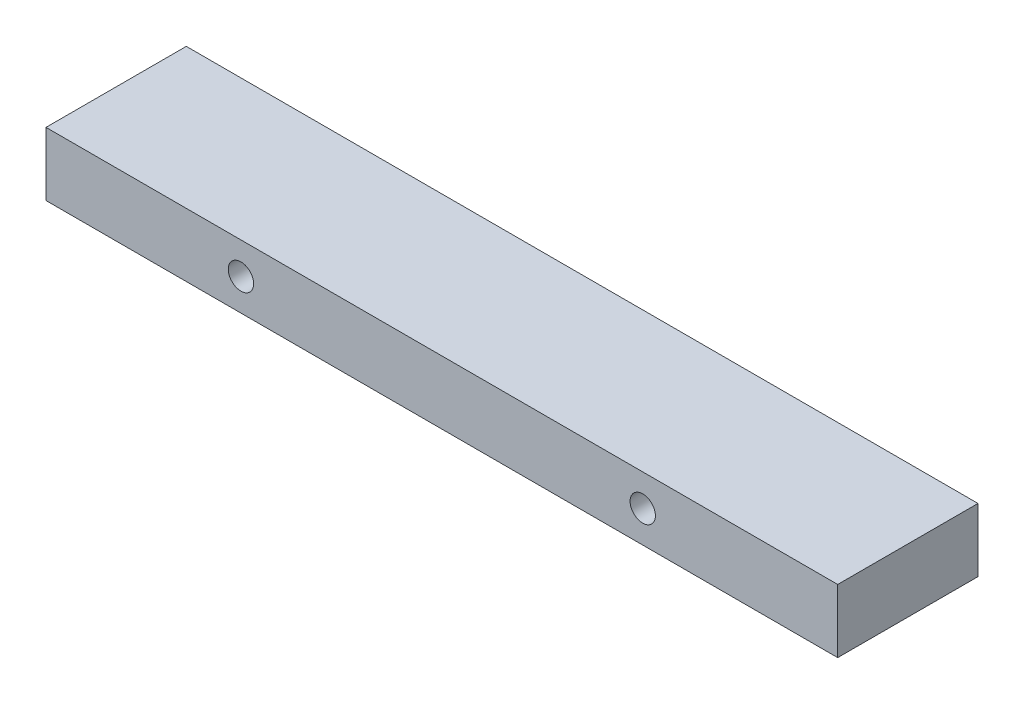
SolidWorks part; units mm, degrees
material "6061-T6 (SS)"
ref_plane "前视基准面" through (0, 0, 0) normal (0, 0, 1) x (1, 0, 0)
ref_plane "上视基准面" through (0, 0, 0) normal (0, 1, 0) x (1, 0, 0)
ref_plane "右视基准面" through (0, 0, 0) normal (1, 0, 0) x (0, 0, -1)
other "Configuration Table"
sketch "草图1" plane through (0, 0, 0) normal (0, 0, 1) x (1, 0, 0)
  line L1 (-0.3, -4.3) -> (49.65, -4.3)
  line L2 (-0.3, -4.3) -> (-0.3, -0.3)
  line L3 (-0.3, -0.3) -> (49.65, -0.3)
  line L4 (49.65, -4.3) -> (49.65, -0.3)
  dimension "D1" = 49.65
  dimension "D2" = 0.3
  dimension "D3" = 0.3
  dimension "D4" = 4.3
extrude "Front_Plate" add sketch "草图1" along normal blind 8.8519
move or copy body "Stock_Z_Position" bodies to move or copy 106 copy no translate (0, 0, 2.2481) parameters "D1"=0, "D2"=0, "D3"=2.2481
sketch "草图2" plane through (0, 0, 11.1) normal (0, 0, 1) x (1, 0, 0)
  circle A0 centre (12, -2.3) radius 0.8
  circle A1 centre (37.35, -2.3) radius 0.8
  dimension "D1" = 1.6
  dimension "D2" = 12
  dimension "D3" = 37.35
  dimension "D4" = 2.3
extrude "Frame_2xD1p6_Through" cut sketch "草图2" against normal through all
cosmetic thread "Frame_M2_Through_Cosmetic_1" parameters "D2"=2
cosmetic thread "Frame_M2_Through_Cosmetic_2" parameters "D2"=2
